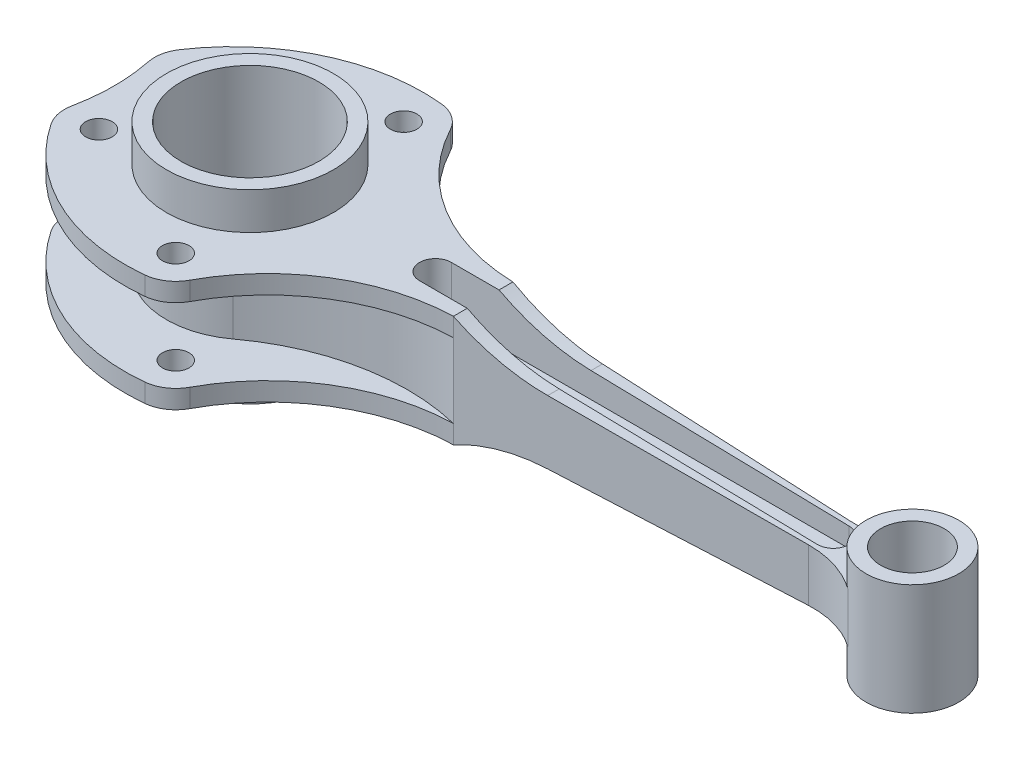
SolidWorks part; units mm, degrees
ref_plane "Front Plane" through (0, 0, 0) normal (0, 0, 1) x (1, 0, 0)
ref_plane "Top Plane" through (0, 0, 0) normal (0, 1, 0) x (1, 0, 0)
ref_plane "Right Plane" through (0, 0, 0) normal (1, 0, 0) x (0, 0, -1)
sketch "Sketch1" plane through (0, 0, 0) normal (0, 1, 0) x (1, 0, 0)
  line L0 (-250, 0) -> (0, 0) construction
  line L1 (-31.3121, 7.8179) -> (-162, 11.24)
  line L2 (-180, 0) -> (-30, 0) construction
  line L3 (-180, 6) -> (-30, 6)
  line L4 (-180, -6) -> (-30, -6)
  line L5 (-31.3121, -7.8179) -> (-162, -11.24)
  circle A0 centre (0, 0) radius 12
  circle A1 centre (0, 0) radius 17.5
  circle A2 centre (-250, 0) radius 26
  circle A3 centre (-250, 0) radius 31.5
  arc A4 (-10.132, 14.2686) -> (-31.3121, 7.8179) centre (-30.3959, 42.8059) cw
  arc A5 (-180, 6) -> (-180, -6) centre (-180, 0) ccw
  arc A6 (-30, -6) -> (-30, 6) centre (-30, 0) ccw
  arc A7 (-162, 11.24) -> (-223.547, 49.1506) centre (-160.1153, 83.2154) cw
  arc A8 (-223.547, 49.1506) -> (-233.7013, 55.935) centre (-235, 43) ccw
  arc A9 (-233.7013, 55.935) -> (-300.82, 24.2062) centre (-240.8941, -15.7049) ccw
  arc A10 (-300.82, 24.2062) -> (-302.7373, 14.4) centre (-290, 17) ccw
  arc A11 (-302.7373, 14.4) -> (-302.7373, -14.4) centre (-373.2827, 0) cw
  arc A12 (-223.547, -49.1506) -> (-233.7013, -55.935) centre (-235, -43) cw
  arc A13 (-300.82, -24.2062) -> (-302.7373, -14.4) centre (-290, -17) cw
  arc A14 (-233.7013, -55.935) -> (-300.82, -24.2062) centre (-240.8941, 15.7049) cw
  arc A15 (-162, -11.24) -> (-223.547, -49.1506) centre (-160.1153, -83.2154) ccw
  arc A16 (-231.2016, -25.2759) -> (-162, -11.24) centre (-181.6692, -91.8758) cw
  circle A17 centre (-290, 17) radius 5
  circle A18 centre (-235, 43) radius 5
  circle A19 centre (-290, -17) radius 5
  circle A20 centre (-235, -43) radius 5
  arc A21 (-231.2016, 25.2759) -> (-162, 11.24) centre (-181.6692, 91.8758) ccw
  arc A22 (-10.132, -14.2686) -> (-31.3121, -7.8179) centre (-30.3959, -42.8059) ccw
  point P12 (-105, 0)
  point P44 (0, 0)
  point P45 (0, 0)
  point P51 (0, 0)
  dimension "D1" = 24
  dimension "D2" = 35
  dimension "D3" = 63
  dimension "D4" = 52
  dimension "D5" = 250
  dimension "D6" = 35
  dimension "D11" = 72
  dimension "D12" = 13
  dimension "D18" = 83
  dimension "D17" = 10
  dimension "D7" = 1.5
  dimension "D8" = 12
  dimension "D9" = 150
  dimension "D10" = 30
  dimension "D13" = 15
  dimension "D14" = 40
  dimension "D15" = 26
  dimension "D16" = 43
  dimension "D19" = 88
extrude "Boss-Extrude1" add sketch "Sketch1" along normal mid plane 42 contours A1 A0 region at (7.8022, 0, -15.1095)
extrude "Boss-Extrude2" add sketch "Sketch1<3>" along normal mid plane 70 separate body contours A3 A2 region at (-222.65, 0, -13.7438)
sketch "Sketch1<3>" plane through (0, 0, 0) normal (0, 1, 0) x (1, 0, 0) same geometry as "Sketch1"
extrude "Boss-Extrude3" add sketch "Sketch1<4>" along normal mid plane 42 contours A3 A21 A7 A8 A9 A10 A11 A13 A14 A12 A15 A16 A17 A18 A19 A20 | A22 A1 A4 L1 A7 A21 A3 A16 A15 L5 A6 L4 A5 L3 region at (-19.5378, 0, -7.155) region at (-197.8091, 0, -12.3004)
sketch "Sketch1<4>" plane through (0, 0, 0) normal (0, 1, 0) x (1, 0, 0) same geometry as "Sketch1"
extrude "Boss-Extrude4" add sketch "Sketch1<5>" along normal mid plane 5 contours L4 A6 L3 A5 region at (-105, 0, 0)
sketch "Sketch1<5>" plane through (0, 0, 0) normal (0, 1, 0) x (1, 0, 0) same geometry as "Sketch1"
sketch "Sketch3" plane through (0, 0, 0) normal (0, 0, 1) x (1, 0, 0)
  line L0 (0, 0) -> (-10.132, 0) construction
  line L1 (-10.132, 21) -> (-10.132, -21) construction
  line L2 (-10.132, 0) -> (-76.872, 0) construction
  line L3 (-127.2933, 12) -> (17.5, 8.8406)
  line L5 (-127.2933, -12) -> (17.5, -8.8406)
  line L7 (-162, 21) -> (17.5, 21)
  line L8 (17.5, 21) -> (17.5, 8.8406)
  line L9 (17.5, -21) -> (17.5, -8.8406)
  line L10 (-162, -21) -> (17.5, -21)
  arc A0 (-162, 21) -> (-127.2933, 12) centre (-125.5917, 89.9814) ccw
  arc A1 (-162, -21) -> (-127.2933, -12) centre (-125.5917, -89.9814) cw
  dimension "D1" = 78
  dimension "D2" = 1.25
  dimension "D3" = 24
extrude "Cut-Extrude1" cut sketch "Sketch3" against normal through all both and the other way through all contours A1 L10 L9 L5 | L7 L8 L3 A0 region at (-61.8562, -15.8807, 0)
extrude "Boss-Extrude5" add sketch "Sketch1<6>" along normal mid plane 42 contours A1 A0 region at (7.8022, 0, -15.1095)
sketch "Sketch1<6>" plane through (0, 0, 0) normal (0, 1, 0) x (1, 0, 0) same geometry as "Sketch1"
extrude "Cut-Extrude2" cut sketch "Sketch1<7>" against normal mid plane 28 contours A3 A21 A7 A8 A9 A10 A11 A13 A14 A12 A15 A16 A17 A18 A19 A20 region at (-197.8091, 0, -12.3004)
sketch "Sketch1<7>" plane through (0, 0, 0) normal (0, 1, 0) x (1, 0, 0) same geometry as "Sketch1"
